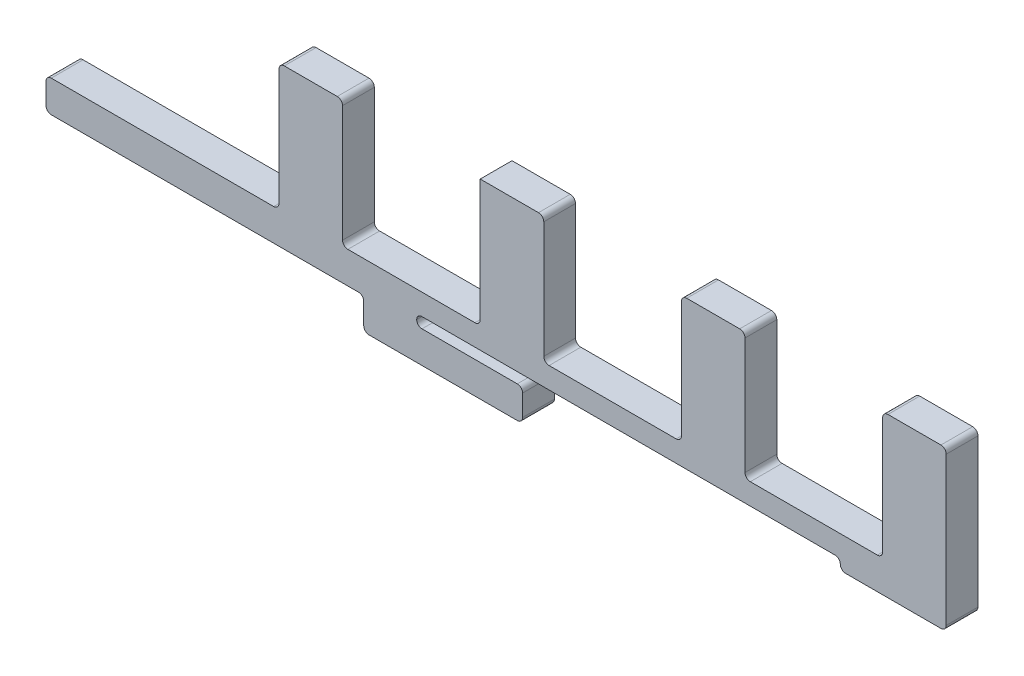
SolidWorks part; units mm, degrees
ref_plane "Front Plane" through (0, 0, 0) normal (0, 0, 1) x (1, 0, 0)
ref_plane "Top Plane" through (0, 0, 0) normal (0, 1, 0) x (1, 0, 0)
ref_plane "Right Plane" through (0, 0, 0) normal (1, 0, 0) x (0, 0, -1)
sketch "Sketch1" plane through (0, 0, 0) normal (0, 0, 1) x (1, 0, 0)
  line L0 (0, 0) -> (30, 0)
  line L1 (85, 0) -> (85, 15)
  line L2 (85, 15) -> (79, 15)
  line L3 (79, 15) -> (79, 3)
  line L4 (79, 3) -> (66, 3)
  line L5 (66, 3) -> (66, 15)
  line L6 (66, 15) -> (60, 15)
  line L7 (60, 15) -> (60, 3)
  line L8 (75, 0) -> (75, 1)
  line L12 (30, 0) -> (30, -3)
  line L14 (75, 1) -> (35, 1)
  line L16 (75, 0) -> (85, 0)
  line L17 (60, 3) -> (47, 3)
  line L18 (47, 3) -> (47, 15)
  line L19 (47, 15) -> (41, 15)
  line L20 (41, 15) -> (41, 3)
  line L21 (41, 3) -> (28, 3)
  line L22 (28, 3) -> (28, 15)
  line L23 (28, 15) -> (22, 15)
  line L24 (22, 15) -> (22, 3)
  line L25 (22, 3) -> (0, 3)
  line L26 (0, 3) -> (0, 0)
  line L27 (30, -3) -> (45, -3)
  line L28 (45, -3) -> (45, 0)
  line L29 (45, 0) -> (35, 0)
  line L30 (35, 0) -> (35, 1)
  dimension "D1" = 85
  dimension "D2" = 5
  dimension "D3" = 10
  dimension "D4" = 3
  dimension "D5" = 8
  dimension "D6" = 40
  dimension "D7" = 8
  dimension "D9" = 6
  dimension "D10" = 13
  dimension "D11" = 6
  dimension "D12" = 15
  dimension "D13" = 3
  dimension "D14" = 3
  dimension "D15" = 1
extrude "Boss-Extrude1" add sketch "Sketch1" along normal blind 3
fillet "Fillet1" radius 0.5 25 edges at (22, 3, 1.5) (22, 15, 1.5) (28, 15, 1.5) (28, 3, 1.5) (41, 3, 1.5) (47, 15, 1.5) (47, 3, 1.5) (66, 3, 1.5) (60, 3, 1.5) (60, 15, 1.5) (66, 15, 1.5) (79, 3, 1.5) (79, 15, 1.5) (85, 15, 1.5) (85, 0, 1.5) (75, 1, 1.5) (75, 0, 1.5) (0, 3, 1.5) (0, 0, 1.5) (30, 0, 1.5) (30, -3, 1.5) (45, -3, 1.5) (45, 0, 1.5) (35, 0, 1.5) (35, 1, 1.5)
